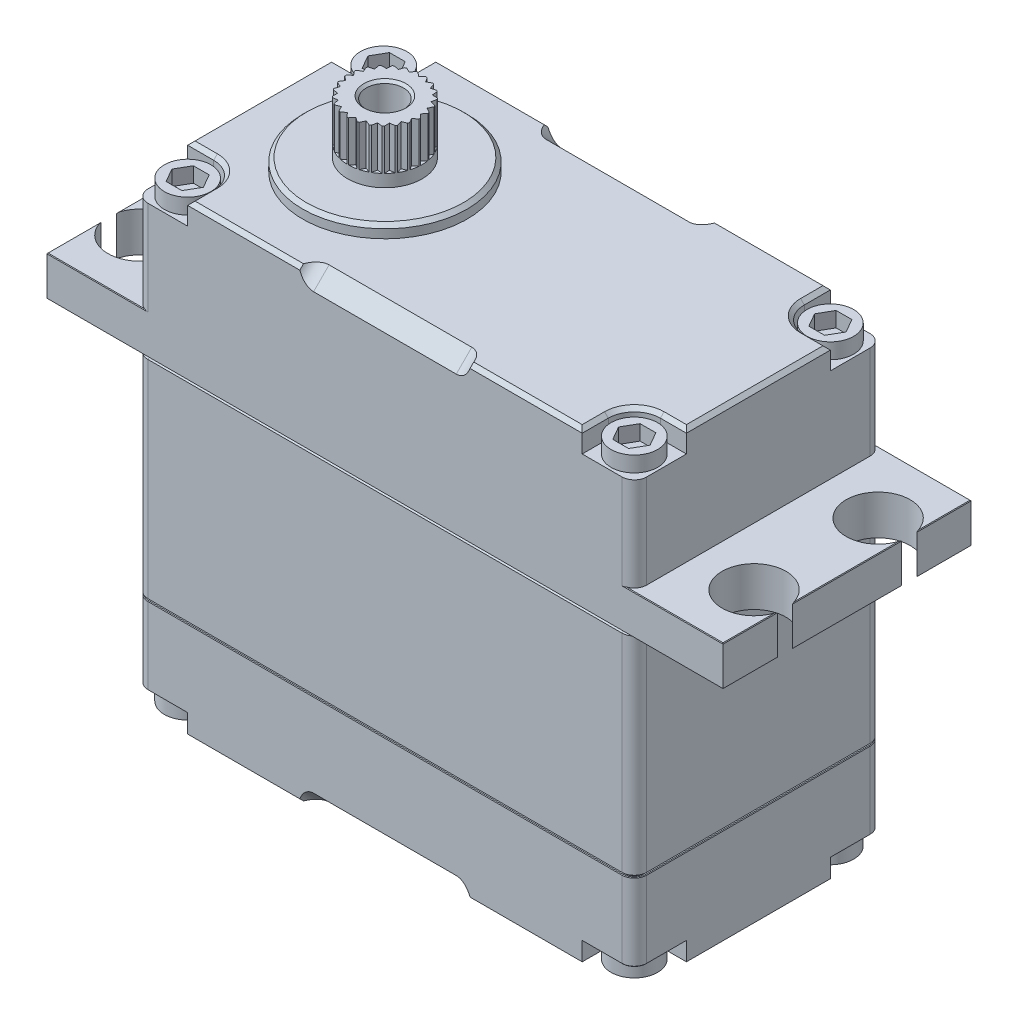
SolidWorks part; units mm, degrees
material "Nylon 101"
ref_plane "Front Plane" through (0, 0, 0) normal (0, 0, 1) x (1, 0, 0)
ref_plane "Top Plane" through (0, 0, 0) normal (0, 1, 0) x (1, 0, 0)
ref_plane "Right Plane" through (0, 0, 0) normal (1, 0, 0) x (0, 0, -1)
sketch "Sketch1" plane through (0, 0, 0) normal (0, 1, 0) x (1, 0, 0)
  line L1 (0, 0) -> (40.2, 0)
  line L2 (0, 0) -> (0, 20)
  line L3 (0, 20) -> (40.2, 20)
  line L4 (40.2, 0) -> (40.2, 20)
  dimension "D1" = 20
  dimension "D2" = 40.2
extrude "Boss-Extrude1" add sketch "Sketch1" along normal blind 9.3
sketch "Sketch2" plane through (0, 0, 0) normal (0, -1, 0) x (1, 0, 0)
  line L0 (40.2, -20) -> (0, -20) construction
  line L1 (-7.15, 0) -> (47.35, 0)
  line L2 (-7.15, 0) -> (-7.15, -20)
  line L3 (-7.15, -20) -> (47.35, -20)
  line L4 (47.35, 0) -> (47.35, -20)
  line L6 (0, 0) -> (40.2, 0) construction
  point P8 (20.1, 0)
  point P9 (20.1, 0)
  dimension "D1" = 54.5
extrude "Boss-Extrude2" add sketch "Sketch2" along normal blind 3.2
sketch "Sketch3" plane through (0, -3.2, 0) normal (0, -1, 0) x (1, 0, 0)
  line L4 (0, 0) -> (0, -20)
  line L5 (40.2, 0) -> (0, 0)
  line L6 (40.2, -20) -> (40.2, 0)
  line L7 (0, -20) -> (40.2, -20)
  line L8 (0, 0) -> (0, -20)
  line L9 (40.2, 0) -> (0, 0)
  line L10 (40.2, -20) -> (40.2, 0)
  line L11 (0, -20) -> (40.2, -20)
  dimension "D1" = 0
extrude "Boss-Extrude3" add sketch "Sketch3" along normal blind 17 separate body
sketch "Sketch4" plane through (0, -20.2, 0) normal (0, -1, 0) x (1, 0, 0)
  line L4 (0, -20) -> (40.2, -20)
  line L5 (40.2, -20) -> (40.2, 0)
  line L6 (40.2, 0) -> (0, 0)
  line L7 (0, 0) -> (0, -20)
  line L8 (0, -20) -> (40.2, -20)
  line L9 (40.2, -20) -> (40.2, 0)
  line L10 (40.2, 0) -> (0, 0)
  line L11 (0, 0) -> (0, -20)
  dimension "D1" = 0
extrude "Boss-Extrude5" add sketch "Sketch4" along normal blind 8 separate body
sketch "Sketch5" plane through (0, 9.3, 0) normal (0, 1, 0) x (1, 0, 0)
  line L0 (-7.15, 0) -> (-7.15, 20) construction
  circle A0 centre (10.1, 10) radius 6.625
  point P4 (-7.15, 10)
  dimension "D1" = 13.25
  dimension "D2" = 17.25
extrude "Boss-Extrude6" add sketch "Sketch5" along normal blind 1
sketch "Sketch6" plane through (0, 10.3, 0) normal (0, 1, 0) x (1, 0, 0)
  circle A0 centre (10.1, 10) radius 3
  circle A1 centre (10.1, 10) radius 6.625
  circle A2 centre (10.1, 10) radius 6.625 construction
  dimension "D2" = 6
  dimension "D1" = 0
extrude "Boss-Extrude7" add sketch "Sketch6" along normal blind 4.3 separate body
sketch "Sketch7" plane through (0, 0, 0) normal (0, 1, 0) x (1, 0, 0)
  line L0 (40.2, 20) -> (0, 20) construction
  line L1 (-4.65, 15) -> (44.85, 15) construction
  line L2 (-4.65, 15) -> (-4.65, 5) construction
  line L3 (-4.65, 5) -> (44.85, 5) construction
  line L4 (44.85, 15) -> (44.85, 5) construction
  line L5 (20.1, 20) -> (20.1, 0) construction
  line L6 (0, 0) -> (40.2, 0) construction
  circle A0 centre (-4.65, 5) radius 2.575
  circle A1 centre (-4.65, 15) radius 2.575
  circle A2 centre (44.85, 15) radius 2.575
  circle A3 centre (44.85, 5) radius 2.575
  point P10 (20.1, 20)
  point P11 (20.1, 15)
  point P16 (20.1, 10)
  point P17 (44.85, 10)
  dimension "D3" = 5.15
  dimension "D1" = 49.5
  dimension "D2" = 10
extrude "Cut-Extrude1" cut sketch "Sketch7" against normal up to next (3.2 mm away)
sketch "Sketch9" plane through (0, 14.6, 0) normal (0, 1, 0) x (1, 0, 0)
  circle A0 centre (10.1, 10) radius 1.5
  dimension "D1" = 3
extrude "Cut-Extrude3" cut sketch "Sketch9" against normal blind 4
chamfer "Chamfer1" distance 0.2 angle 45 1 edges at (10.1, 14.6, -8.5)
sketch "Sketch10" plane through (40.2, 0, 0) normal (1, 0, 0) x (0, 0, -1)
  line L1 (7, -20.2) -> (13, -20.2)
  line L2 (7, -20.2) -> (7, -23.2)
  line L3 (7, -23.2) -> (13, -23.2)
  line L4 (13, -20.2) -> (13, -23.2)
  line L5 (20, -20.2) -> (0, -20.2) construction
  point P9 (10, -20.2)
  point P10 (10, -20.2)
  dimension "D1" = 3
  dimension "D2" = 6
extrude "Boss-Extrude8" add sketch "Sketch10" against normal blind 5 from surface at -40.2 separate body starting at face at (0, -24.2, -10)
sketch "Sketch8" plane through (0, 14.6, 0) normal (0, 1, 0) x (1, 0, 0)
  line L0 (10.1, 10) -> (10.1, 13) construction
  line L1 (9.775, 13) -> (10.425, 13)
  line L2 (10.425, 13) -> (10.1, 12.7)
  line L3 (10.1, 12.7) -> (9.775, 13)
  line L4 (10.7715, 12.6152) -> (10.5313, 12.9866)
  line L5 (10.5313, 12.9866) -> (11.1609, 12.8249)
  line L6 (11.1609, 12.8249) -> (10.7715, 12.6152)
  line L7 (11.4007, 12.366) -> (11.2605, 12.7855)
  line L8 (11.2605, 12.7855) -> (11.8301, 12.4724)
  line L9 (11.8301, 12.4724) -> (11.4007, 12.366)
  line L10 (11.9483, 11.9682) -> (11.9167, 12.4094)
  line L11 (11.9167, 12.4094) -> (12.3906, 11.9644)
  line L12 (12.3906, 11.9644) -> (11.9483, 11.9682)
  line L13 (12.3797, 11.4467) -> (12.4588, 11.8819)
  line L14 (12.4588, 11.8819) -> (12.8071, 11.3331)
  line L15 (12.8071, 11.3331) -> (12.3797, 11.4467)
  line L16 (12.6679, 10.8343) -> (12.8527, 11.2361)
  line L17 (12.8527, 11.2361) -> (13.0536, 10.618)
  line L18 (13.0536, 10.618) -> (12.6679, 10.8343)
  line L19 (12.7947, 10.1695) -> (13.0737, 10.5127)
  line L20 (13.0737, 10.5127) -> (13.1145, 9.864)
  line L21 (13.1145, 9.864) -> (12.7947, 10.1695)
  line L22 (12.7522, 9.4941) -> (13.1078, 9.7571)
  line L23 (13.1078, 9.7571) -> (12.986, 9.1186)
  line L24 (12.986, 9.1186) -> (12.7522, 9.4941)
  line L25 (12.543, 8.8504) -> (12.9529, 9.0167)
  line L26 (12.9529, 9.0167) -> (12.6761, 8.4286)
  line L27 (12.6761, 8.4286) -> (12.543, 8.8504)
  line L28 (12.1804, 8.279) -> (12.6187, 8.3381)
  line L29 (12.6187, 8.3381) -> (12.2044, 7.8373)
  line L30 (12.2044, 7.8373) -> (12.1804, 8.279)
  line L31 (11.687, 7.8157) -> (12.1263, 7.764)
  line L32 (12.1263, 7.764) -> (11.6004, 7.3819)
  line L33 (11.6004, 7.3819) -> (11.687, 7.8157)
  line L34 (11.0939, 7.4896) -> (11.5066, 7.3303)
  line L35 (11.5066, 7.3303) -> (10.9022, 7.091)
  line L36 (10.9022, 7.091) -> (11.0939, 7.4896)
  line L37 (10.4384, 7.3213) -> (10.7984, 7.0644)
  line L38 (10.7984, 7.0644) -> (10.1536, 6.9829)
  line L39 (10.1536, 6.9829) -> (10.4384, 7.3213)
  line L40 (9.7616, 7.3213) -> (10.0464, 6.9829)
  line L41 (10.0464, 6.9829) -> (9.4016, 7.0644)
  line L42 (9.4016, 7.0644) -> (9.7616, 7.3213)
  line L43 (9.1061, 7.4896) -> (9.2978, 7.091)
  line L44 (9.2978, 7.091) -> (8.6934, 7.3303)
  line L45 (8.6934, 7.3303) -> (9.1061, 7.4896)
  line L46 (8.513, 7.8157) -> (8.5996, 7.3819)
  line L47 (8.5996, 7.3819) -> (8.0737, 7.764)
  line L48 (8.0737, 7.764) -> (8.513, 7.8157)
  line L49 (8.0196, 8.279) -> (7.9956, 7.8373)
  line L50 (7.9956, 7.8373) -> (7.5813, 8.3381)
  line L51 (7.5813, 8.3381) -> (8.0196, 8.279)
  line L52 (7.657, 8.8504) -> (7.5239, 8.4286)
  line L53 (7.5239, 8.4286) -> (7.2471, 9.0167)
  line L54 (7.2471, 9.0167) -> (7.657, 8.8504)
  line L55 (7.4478, 9.4941) -> (7.214, 9.1186)
  line L56 (7.214, 9.1186) -> (7.0922, 9.7571)
  line L57 (7.0922, 9.7571) -> (7.4478, 9.4941)
  line L58 (7.4053, 10.1695) -> (7.0855, 9.864)
  line L59 (7.0855, 9.864) -> (7.1263, 10.5127)
  line L60 (7.1263, 10.5127) -> (7.4053, 10.1695)
  line L61 (7.5321, 10.8343) -> (7.1464, 10.618)
  line L62 (7.1464, 10.618) -> (7.3473, 11.2361)
  line L63 (7.3473, 11.2361) -> (7.5321, 10.8343)
  line L64 (7.8203, 11.4467) -> (7.3929, 11.3331)
  line L65 (7.3929, 11.3331) -> (7.7412, 11.8819)
  line L66 (7.7412, 11.8819) -> (7.8203, 11.4467)
  line L67 (8.2517, 11.9682) -> (7.8094, 11.9644)
  line L68 (7.8094, 11.9644) -> (8.2833, 12.4094)
  line L69 (8.2833, 12.4094) -> (8.2517, 11.9682)
  line L70 (8.7993, 12.366) -> (8.3699, 12.4724)
  line L71 (8.3699, 12.4724) -> (8.9395, 12.7855)
  line L72 (8.9395, 12.7855) -> (8.7993, 12.366)
  line L73 (9.4285, 12.6152) -> (9.0391, 12.8249)
  line L74 (9.0391, 12.8249) -> (9.6687, 12.9866)
  line L75 (9.6687, 12.9866) -> (9.4285, 12.6152)
  circle A0 centre (10.1, 10) radius 3 construction
  point P7 (10.1, 13)
  point P84 (10.1, 10)
  dimension "D1" = 0.3
  dimension "D2" = 0.65
  dimension "D3" = 25
extrude "Cut-Extrude2" cut sketch "Sketch8" against normal blind 3.3
sketch "Sketch11" plane through (0, 9.3, 0) normal (0, 1, 0) x (1, 0, 0)
  line L0 (20.1, 20) -> (20.1, 0) construction
  line L1 (40.2, 20) -> (0, 20) construction
  line L2 (0, 0) -> (40.2, 0) construction
  line L3 (0, 10) -> (40.2, 10) construction
  line L4 (0, 20) -> (0, 0) construction
  line L5 (40.2, 0) -> (40.2, 20) construction
  line L6 (36, 2.1) -> (36, 0)
  line L7 (36, 0) -> (40.2, 0)
  line L9 (38.1, 4.2) -> (40.2, 4.2)
  line L10 (40.2, 0) -> (40.2, 20) construction
  line L11 (40.2, 4.2) -> (40.2, 0)
  line L12 (38.1, 15.8) -> (40.2, 15.8)
  line L13 (40.2, 15.8) -> (40.2, 20)
  line L14 (36, 20) -> (40.2, 20)
  line L15 (36, 17.9) -> (36, 20)
  line L16 (2.1, 4.2) -> (0, 4.2)
  line L17 (0, 4.2) -> (0, 0)
  line L18 (4.2, 0) -> (0, 0)
  line L19 (4.2, 2.1) -> (4.2, 0)
  line L20 (4.2, 17.9) -> (4.2, 20)
  line L21 (4.2, 20) -> (0, 20)
  line L22 (0, 15.8) -> (0, 20)
  line L23 (2.1, 15.8) -> (0, 15.8)
  arc A0 (38.1, 4.2) -> (36, 2.1) centre (38.1, 2.1) ccw
  arc A1 (38.1, 15.8) -> (36, 17.9) centre (38.1, 17.9) cw
  arc A2 (2.1, 4.2) -> (4.2, 2.1) centre (2.1, 2.1) cw
  arc A3 (2.1, 15.8) -> (4.2, 17.9) centre (2.1, 17.9) ccw
  dimension "D1" = 4.2
extrude "Cut-Extrude4" cut sketch "Sketch11" against normal blind 1.75
sketch "Sketch13" plane through (0, -28.2, 0) normal (0, -1, 0) x (1, 0, 0)
  line L0 (38.1, -15.8) -> (40.2, -15.8) construction
  line L1 (40.2, -15.8) -> (40.2, -20) construction
  line L2 (40.2, -20) -> (36, -20) construction
  line L3 (36, -20) -> (36, -17.9) construction
  line L4 (36, -2.1) -> (36, 0) construction
  line L5 (36, 0) -> (40.2, 0) construction
  line L6 (40.2, 0) -> (40.2, -4.2) construction
  line L7 (40.2, -4.2) -> (38.1, -4.2) construction
  line L8 (2.1, -4.2) -> (0, -4.2) construction
  line L9 (0, -4.2) -> (0, 0) construction
  line L10 (0, 0) -> (4.2, 0) construction
  line L11 (4.2, 0) -> (4.2, -2.1) construction
  line L12 (4.2, -17.9) -> (4.2, -20) construction
  line L13 (4.2, -20) -> (0, -20) construction
  line L14 (0, -20) -> (0, -15.8) construction
  line L15 (0, -15.8) -> (2.1, -15.8) construction
  line L16 (38.1, -15.8) -> (40.2, -15.8)
  line L17 (40.2, -15.8) -> (40.2, -20)
  line L18 (40.2, -20) -> (36, -20)
  line L19 (36, -20) -> (36, -17.9)
  line L20 (36, -2.1) -> (36, 0)
  line L21 (36, 0) -> (40.2, 0)
  line L22 (40.2, 0) -> (40.2, -4.2)
  line L23 (40.2, -4.2) -> (38.1, -4.2)
  line L24 (2.1, -4.2) -> (0, -4.2)
  line L25 (0, -4.2) -> (0, 0)
  line L26 (0, 0) -> (4.2, 0)
  line L27 (4.2, 0) -> (4.2, -2.1)
  line L28 (4.2, -17.9) -> (4.2, -20)
  line L29 (4.2, -20) -> (0, -20)
  line L30 (0, -20) -> (0, -15.8)
  line L31 (0, -15.8) -> (2.1, -15.8)
  arc A0 (38.1, -15.8) -> (36, -17.9) centre (38.1, -17.9) ccw construction
  arc A1 (36, -2.1) -> (38.1, -4.2) centre (38.1, -2.1) ccw construction
  arc A2 (2.1, -4.2) -> (4.2, -2.1) centre (2.1, -2.1) ccw construction
  arc A3 (4.2, -17.9) -> (2.1, -15.8) centre (2.1, -17.9) ccw construction
  arc A4 (38.1, -15.8) -> (36, -17.9) centre (38.1, -17.9) ccw
  arc A5 (36, -2.1) -> (38.1, -4.2) centre (38.1, -2.1) ccw
  arc A6 (2.1, -4.2) -> (4.2, -2.1) centre (2.1, -2.1) ccw
  arc A7 (4.2, -17.9) -> (2.1, -15.8) centre (2.1, -17.9) ccw
extrude "Cut-Extrude6" cut sketch "Sketch13" against normal blind 1.75
sketch "Sketch12" plane through (0, 9.3, 0) normal (0, 1, 0) x (1, 0, 0)
  line L0 (0, 10) -> (40.2, 10) construction
  line L1 (0, 15.8) -> (0, 4.2) construction
  line L2 (40.2, 4.2) -> (40.2, 15.8) construction
  line L3 (36, 20) -> (4.2, 20) construction
  line L4 (13.1, 20) -> (27.1, 20)
  line L5 (13.1, 20) -> (13.1, 18.75)
  line L6 (13.1, 18.75) -> (27.1, 18.75)
  line L7 (27.1, 20) -> (27.1, 18.75)
  line L8 (13.1, 1.25) -> (27.1, 1.25)
  line L9 (27.1, 0) -> (27.1, 1.25)
  line L10 (13.1, 0) -> (27.1, 0)
  line L11 (13.1, 0) -> (13.1, 1.25)
  point P12 (20.1, 20)
  point P13 (20.1, 10)
  dimension "D1" = 1.25
  dimension "D2" = 14
extrude "Cut-Extrude5" cut sketch "Sketch12" against normal blind 1.25
sketch "Sketch14" plane through (0, -28.2, 0) normal (0, -1, 0) x (1, 0, 0)
  line L0 (13.1, -20) -> (13.1, -18.75) construction
  line L1 (13.1, -18.75) -> (27.1, -18.75) construction
  line L2 (27.1, -18.75) -> (27.1, -20) construction
  line L3 (27.1, -20) -> (13.1, -20) construction
  line L4 (13.1, -1.25) -> (13.1, 0) construction
  line L5 (13.1, 0) -> (27.1, 0) construction
  line L6 (27.1, 0) -> (27.1, -1.25) construction
  line L7 (27.1, -1.25) -> (13.1, -1.25) construction
  line L8 (13.1, -20) -> (13.1, -18.75)
  line L9 (13.1, -18.75) -> (27.1, -18.75)
  line L10 (27.1, -18.75) -> (27.1, -20)
  line L11 (27.1, -20) -> (13.1, -20)
  line L12 (13.1, -1.25) -> (13.1, 0)
  line L13 (13.1, 0) -> (27.1, 0)
  line L14 (27.1, 0) -> (27.1, -1.25)
  line L15 (27.1, -1.25) -> (13.1, -1.25)
extrude "Cut-Extrude7" cut sketch "Sketch14" against normal blind 1.25
chamfer "Chamfer2" distance 1.25 angle 45 2 edges at (20.1, 8.05, -1.25) (20.1, 8.05, -18.75)
chamfer "Chamfer3" distance 1.25 angle 45 2 edges at (20.1, -26.95, -1.25) (20.1, -26.95, -18.75)
fillet "Fillet1" radius 1.25 4 edges at (13.1, 8.675, -0.625) (27.1, 8.675, -0.625) (13.1, 8.675, -19.375) (27.1, 8.675, -19.375)
chamfer "Chamfer5" distance 0.3 angle 45 19 edges at (31.5226, 9.3, 0) (39.15, 9.3, -4.2) (36, 9.3, -1.05) (36.6151, 9.3, -3.5849) (40.2, 9.3, -10) (36, 9.3, -18.95) (39.15, 9.3, -15.8) (36.6151, 9.3, -16.4151) (31.5226, 9.3, -20) (1.05, 9.3, -15.8) (4.2, 9.3, -18.95) (3.5849, 9.3, -16.4151) (8.6774, 9.3, -20) (0, 9.3, -10) (4.2, 9.3, -1.05) (1.05, 9.3, -4.2) (3.5849, 9.3, -3.5849) (8.6774, 9.3, 0) (10.1, 10.3, -3.375)
fillet "Fillet2" radius 1.25 4 edges at (13.1, -27.575, -19.375) (27.1, -27.575, -19.375) (27.1, -27.575, -0.625) (13.1, -27.575, -0.625)
chamfer "Chamfer6" distance 0.3 angle 45 18 edges at (40.2, -28.2, -10) (36, -28.2, -1.05) (39.15, -28.2, -4.2) (36.6151, -28.2, -3.5849) (31.5226, -28.2, 0) (39.15, -28.2, -15.8) (36.6151, -28.2, -16.4151) (36, -28.2, -18.95) (31.5226, -28.2, -20) (8.6774, -28.2, -20) (4.2, -28.2, -18.95) (3.5849, -28.2, -16.4151) (1.05, -28.2, -15.8) (0, -28.2, -10) (1.05, -28.2, -4.2) (3.5849, -28.2, -3.5849) (4.2, -28.2, -1.05) (8.6774, -28.2, 0)
fillet "Fillet3" radius 1 4 edges at (40.2, -11.7, 0) (40.2, -11.7, -20) (0, -11.7, 0) (0, -11.7, -20)
fillet "Fillet4" radius 1 4 edges at (0, -23.325, 0) (40.2, -23.325, 0) (40.2, -23.325, -20) (0, -23.325, -20)
fillet "Fillet5" radius 1 4 edges at (0, 3.775, 0) (0, 3.775, -20) (40.2, 3.775, -20) (40.2, 3.775, 0)
sketch "Sketch15" plane through (0, 7.55, 0) normal (0, 1, 0) x (1, 0, 0)
  line L0 (40.2, 15.8) -> (40.2, 19) construction
  line L1 (39.2, 20) -> (36, 20) construction
  line L2 (36, 20) -> (36, 17.9) construction
  line L3 (38.1, 15.8) -> (40.2, 15.8) construction
  line L4 (4.2, 20) -> (1, 20) construction
  line L5 (0, 19) -> (0, 15.8) construction
  line L6 (0, 15.8) -> (2.1, 15.8) construction
  line L7 (4.2, 17.9) -> (4.2, 20) construction
  line L8 (0, 4.2) -> (0, 1) construction
  line L9 (1, 0) -> (4.2, 0) construction
  line L10 (4.2, 0) -> (4.2, 2.1) construction
  line L11 (2.1, 4.2) -> (0, 4.2) construction
  line L12 (36, 0) -> (39.2, 0) construction
  line L13 (40.2, 1) -> (40.2, 4.2) construction
  line L14 (40.2, 4.2) -> (38.1, 4.2) construction
  line L15 (36, 2.1) -> (36, 0) construction
  line L16 (40.2, 15.8) -> (40.2, 19) construction
  line L17 (39.2, 20) -> (36, 20) construction
  line L18 (36, 20) -> (36, 17.9) construction
  line L19 (38.1, 15.8) -> (40.2, 15.8) construction
  line L20 (4.2, 20) -> (1, 20) construction
  line L21 (0, 19) -> (0, 15.8) construction
  line L22 (0, 15.8) -> (2.1, 15.8) construction
  line L23 (4.2, 17.9) -> (4.2, 20) construction
  line L24 (0, 4.2) -> (0, 1) construction
  line L25 (1, 0) -> (4.2, 0) construction
  line L26 (4.2, 0) -> (4.2, 2.1) construction
  line L27 (2.1, 4.2) -> (0, 4.2) construction
  line L28 (36, 0) -> (39.2, 0) construction
  line L29 (40.2, 1) -> (40.2, 4.2) construction
  line L30 (40.2, 4.2) -> (38.1, 4.2) construction
  line L31 (36, 2.1) -> (36, 0) construction
  arc A0 (40.2, 19) -> (39.2, 20) centre (39.2, 19) ccw construction
  arc A1 (36, 17.9) -> (38.1, 15.8) centre (38.1, 17.9) ccw construction
  arc A2 (1, 20) -> (0, 19) centre (1, 19) ccw construction
  arc A3 (2.1, 15.8) -> (4.2, 17.9) centre (2.1, 17.9) ccw construction
  arc A4 (0, 1) -> (1, 0) centre (1, 1) ccw construction
  arc A5 (4.2, 2.1) -> (2.1, 4.2) centre (2.1, 2.1) ccw construction
  arc A6 (39.2, 0) -> (40.2, 1) centre (39.2, 1) ccw construction
  arc A7 (38.1, 4.2) -> (36, 2.1) centre (38.1, 2.1) ccw construction
  arc A8 (40.2, 19) -> (39.2, 20) centre (39.2, 19) ccw construction
  arc A9 (36, 17.9) -> (38.1, 15.8) centre (38.1, 17.9) ccw construction
  arc A10 (1, 20) -> (0, 19) centre (1, 19) ccw construction
  arc A11 (2.1, 15.8) -> (4.2, 17.9) centre (2.1, 17.9) ccw construction
  arc A12 (0, 1) -> (1, 0) centre (1, 1) ccw construction
  arc A13 (4.2, 2.1) -> (2.1, 4.2) centre (2.1, 2.1) ccw construction
  arc A14 (39.2, 0) -> (40.2, 1) centre (39.2, 1) ccw construction
  arc A15 (38.1, 4.2) -> (36, 2.1) centre (38.1, 2.1) ccw construction
  circle A16 centre (2.1, 2.1) radius 1.875
  circle A17 centre (2.1, 17.9) radius 1.875
  circle A18 centre (38.1, 17.9) radius 1.875
  circle A19 centre (38.1, 2.1) radius 1.875
  dimension "D1" = 3.75
extrude "Boss-Extrude10" add sketch "Sketch15" along normal blind 1.25 separate body
sketch "Sketch16" plane through (0, -26.45, 0) normal (0, -1, 0) x (1, 0, 0)
  circle A0 centre (2.1, -2.1) radius 1.875 construction
  circle A1 centre (38.1, -2.1) radius 1.875 construction
  circle A2 centre (38.1, -17.9) radius 1.875 construction
  circle A3 centre (2.1, -17.9) radius 1.875 construction
  circle A4 centre (2.1, -2.1) radius 1.875
  circle A5 centre (38.1, -2.1) radius 1.875
  circle A6 centre (38.1, -17.9) radius 1.875
  circle A7 centre (2.1, -17.9) radius 1.875
extrude "Boss-Extrude12" add sketch "Sketch16" along normal blind 1.25 separate body
chamfer "Chamfer8" distance 0.15 angle 45 16 edges at (39.9071, -20.2, -19.7071) (40.2, -20.2, -10) (20.1, -20.2, -20) (39.9071, -20.2, -0.2929) (0.2929, -20.2, -19.7071) (20.1, -20.2, 0) (0, -20.2, -10) (0.2929, -20.2, -0.2929) (40.2, -3.2, -10) (39.9071, -3.2, -0.2929) (39.9071, -3.2, -19.7071) (20.1, -3.2, 0) (20.1, -3.2, -20) (0.2929, -3.2, -0.2929) (0.2929, -3.2, -19.7071) (0, -3.2, -10)
sketch "Sketch18" plane through (0, 8.8, 0) normal (0, 1, 0) x (1, 0, 0)
  line L0 (0.3, 10) -> (39.9, 10) construction
  line L1 (0.3, 15.5) -> (0.3, 4.5) construction
  line L2 (39.9, 4.5) -> (39.9, 15.5) construction
  line L3 (20.1, 18.75) -> (20.1, 1.25) construction
  line L4 (14.35, 18.75) -> (25.85, 18.75) construction
  line L5 (25.85, 1.25) -> (14.35, 1.25) construction
  line L6 (2.7351, 3.2) -> (3.3702, 2.1)
  line L7 (3.3702, 17.9) -> (2.7351, 19)
  line L8 (2.7351, 19) -> (1.4649, 19)
  line L9 (1.4649, 19) -> (0.8298, 17.9)
  line L10 (0.8298, 17.9) -> (1.4649, 16.8)
  line L11 (1.4649, 16.8) -> (2.7351, 16.8)
  line L12 (2.7351, 16.8) -> (3.3702, 17.9)
  line L13 (1.4649, 3.2) -> (2.7351, 3.2)
  line L14 (0.8298, 2.1) -> (1.4649, 3.2)
  line L15 (1.4649, 1) -> (0.8298, 2.1)
  line L16 (2.7351, 1) -> (1.4649, 1)
  line L17 (3.3702, 2.1) -> (2.7351, 1)
  line L18 (38.7351, 3.2) -> (37.4649, 3.2)
  line L19 (39.3702, 2.1) -> (38.7351, 3.2)
  line L20 (38.7351, 1) -> (39.3702, 2.1)
  line L21 (37.4649, 1) -> (38.7351, 1)
  line L22 (36.8298, 2.1) -> (37.4649, 1)
  line L23 (37.4649, 3.2) -> (36.8298, 2.1)
  line L24 (37.4649, 16.8) -> (36.8298, 17.9)
  line L25 (38.7351, 16.8) -> (37.4649, 16.8)
  line L26 (39.3702, 17.9) -> (38.7351, 16.8)
  line L27 (38.7351, 19) -> (39.3702, 17.9)
  line L28 (37.4649, 19) -> (38.7351, 19)
  line L29 (36.8298, 17.9) -> (37.4649, 19)
  circle A1 centre (2.1, 17.9) radius 1.1 construction
  circle A2 centre (2.1, 17.9) radius 1.875
  circle A3 centre (2.1, 17.9) radius 1.875 construction
  dimension "D1" = 0
  dimension "D2" = 2.2
extrude "Cut-Extrude8" cut sketch "Sketch18" against normal blind 1.22
sketch "Sketch19" plane through (0, -27.7, 0) normal (0, -1, 0) x (1, 0, 0)
  line L0 (37.4649, -16.8) -> (38.7351, -16.8) construction
  line L1 (38.7351, -16.8) -> (39.3702, -17.9) construction
  line L2 (39.3702, -17.9) -> (38.7351, -19) construction
  line L3 (38.7351, -19) -> (37.4649, -19) construction
  line L4 (37.4649, -19) -> (36.8298, -17.9) construction
  line L5 (36.8298, -17.9) -> (37.4649, -16.8) construction
  line L6 (39.3702, -2.1) -> (38.7351, -3.2) construction
  line L7 (38.7351, -3.2) -> (37.4649, -3.2) construction
  line L8 (37.4649, -3.2) -> (36.8298, -2.1) construction
  line L9 (36.8298, -2.1) -> (37.4649, -1) construction
  line L10 (37.4649, -1) -> (38.7351, -1) construction
  line L11 (38.7351, -1) -> (39.3702, -2.1) construction
  line L12 (2.7351, -3.2) -> (1.4649, -3.2) construction
  line L13 (1.4649, -3.2) -> (0.8298, -2.1) construction
  line L14 (0.8298, -2.1) -> (1.4649, -1) construction
  line L15 (1.4649, -1) -> (2.7351, -1) construction
  line L16 (2.7351, -1) -> (3.3702, -2.1) construction
  line L17 (3.3702, -2.1) -> (2.7351, -3.2) construction
  line L18 (2.7351, -16.8) -> (3.3702, -17.9) construction
  line L19 (3.3702, -17.9) -> (2.7351, -19) construction
  line L20 (2.7351, -19) -> (1.4649, -19) construction
  line L21 (1.4649, -19) -> (0.8298, -17.9) construction
  line L22 (0.8298, -17.9) -> (1.4649, -16.8) construction
  line L23 (1.4649, -16.8) -> (2.7351, -16.8) construction
  line L24 (37.4649, -16.8) -> (38.7351, -16.8)
  line L25 (38.7351, -16.8) -> (39.3702, -17.9)
  line L26 (39.3702, -17.9) -> (38.7351, -19)
  line L27 (38.7351, -19) -> (37.4649, -19)
  line L28 (37.4649, -19) -> (36.8298, -17.9)
  line L29 (36.8298, -17.9) -> (37.4649, -16.8)
  line L30 (39.3702, -2.1) -> (38.7351, -3.2)
  line L31 (38.7351, -3.2) -> (37.4649, -3.2)
  line L32 (37.4649, -3.2) -> (36.8298, -2.1)
  line L33 (36.8298, -2.1) -> (37.4649, -1)
  line L34 (37.4649, -1) -> (38.7351, -1)
  line L35 (38.7351, -1) -> (39.3702, -2.1)
  line L36 (2.7351, -3.2) -> (1.4649, -3.2)
  line L37 (1.4649, -3.2) -> (0.8298, -2.1)
  line L38 (0.8298, -2.1) -> (1.4649, -1)
  line L39 (1.4649, -1) -> (2.7351, -1)
  line L40 (2.7351, -1) -> (3.3702, -2.1)
  line L41 (3.3702, -2.1) -> (2.7351, -3.2)
  line L42 (2.7351, -16.8) -> (3.3702, -17.9)
  line L43 (3.3702, -17.9) -> (2.7351, -19)
  line L44 (2.7351, -19) -> (1.4649, -19)
  line L45 (1.4649, -19) -> (0.8298, -17.9)
  line L46 (0.8298, -17.9) -> (1.4649, -16.8)
  line L47 (1.4649, -16.8) -> (2.7351, -16.8)
extrude "Cut-Extrude9" cut sketch "Sketch19" against normal blind 1.22
sketch "Sketch23" plane through (0, 14.6, 0) normal (0, 1, 0) x (1, 0, 0)
  line L50 (11.1403, 12.8139) -> (10.7715, 12.6152)
  line L51 (10.7715, 12.6152) -> (10.544, 12.967)
  line L52 (10.4078, 12.9842) -> (10.1, 12.7)
  line L53 (10.1, 12.7) -> (9.7922, 12.9842)
  line L54 (9.656, 12.967) -> (9.4285, 12.6152)
  line L55 (9.4285, 12.6152) -> (9.0597, 12.8139)
  line L56 (8.9321, 12.7633) -> (8.7993, 12.366)
  line L57 (8.7993, 12.366) -> (8.3926, 12.4667)
  line L58 (8.2816, 12.3861) -> (8.2517, 11.9682)
  line L59 (8.2517, 11.9682) -> (7.8328, 11.9646)
  line L60 (7.7453, 11.8589) -> (7.8203, 11.4467)
  line L61 (7.8203, 11.4467) -> (7.4154, 11.3391)
  line L62 (7.357, 11.2149) -> (7.5321, 10.8343)
  line L63 (7.5321, 10.8343) -> (7.1668, 10.6294)
  line L64 (7.1411, 10.4946) -> (7.4053, 10.1695)
  line L65 (7.4053, 10.1695) -> (7.1024, 9.8801)
  line L66 (7.111, 9.7432) -> (7.4478, 9.4941)
  line L67 (7.4478, 9.4941) -> (7.2264, 9.1384)
  line L68 (7.2688, 9.008) -> (7.657, 8.8504)
  line L69 (7.657, 8.8504) -> (7.5309, 8.4509)
  line L70 (7.6044, 8.335) -> (8.0196, 8.279)
  line L71 (8.0196, 8.279) -> (7.9969, 7.8606)
  line L72 (8.0969, 7.7667) -> (8.513, 7.8157)
  line L73 (8.513, 7.8157) -> (8.595, 7.4048)
  line L74 (8.7152, 7.3387) -> (9.1061, 7.4896)
  line L75 (9.1061, 7.4896) -> (9.2877, 7.1121)
  line L76 (9.4206, 7.078) -> (9.7616, 7.3213)
  line L77 (9.7616, 7.3213) -> (10.0314, 7.0008)
  line L78 (10.1686, 7.0008) -> (10.4384, 7.3213)
  line L79 (10.4384, 7.3213) -> (10.7794, 7.078)
  line L80 (10.9123, 7.1121) -> (11.0939, 7.4896)
  line L81 (11.0939, 7.4896) -> (11.4848, 7.3387)
  line L82 (11.605, 7.4048) -> (11.687, 7.8157)
  line L83 (11.687, 7.8157) -> (12.1031, 7.7667)
  line L84 (12.2031, 7.8606) -> (12.1804, 8.279)
  line L85 (12.1804, 8.279) -> (12.5956, 8.335)
  line L86 (12.6691, 8.4509) -> (12.543, 8.8504)
  line L87 (12.543, 8.8504) -> (12.9312, 9.008)
  line L88 (12.9736, 9.1384) -> (12.7522, 9.4941)
  line L89 (12.7522, 9.4941) -> (13.089, 9.7432)
  line L90 (13.0976, 9.8801) -> (12.7947, 10.1695)
  line L91 (12.7947, 10.1695) -> (13.0589, 10.4946)
  line L92 (13.0332, 10.6294) -> (12.6679, 10.8343)
  line L93 (12.6679, 10.8343) -> (12.843, 11.2149)
  line L94 (12.7846, 11.3391) -> (12.3797, 11.4467)
  line L95 (12.3797, 11.4467) -> (12.4547, 11.8589)
  line L96 (12.3672, 11.9646) -> (11.9483, 11.9682)
  line L97 (11.9483, 11.9682) -> (11.9184, 12.3861)
  line L98 (11.8074, 12.4667) -> (11.4007, 12.366)
  line L99 (11.4007, 12.366) -> (11.2679, 12.7633)
  line L100 (11.1403, 12.8139) -> (10.7715, 12.6152)
  line L101 (10.7715, 12.6152) -> (10.544, 12.967)
  line L102 (10.4078, 12.9842) -> (10.1, 12.7)
  line L103 (10.1, 12.7) -> (9.7922, 12.9842)
  line L104 (9.656, 12.967) -> (9.4285, 12.6152)
  line L105 (9.4285, 12.6152) -> (9.0597, 12.8139)
  line L106 (8.9321, 12.7633) -> (8.7993, 12.366)
  line L107 (8.7993, 12.366) -> (8.3926, 12.4667)
  line L108 (8.2816, 12.3861) -> (8.2517, 11.9682)
  line L109 (8.2517, 11.9682) -> (7.8328, 11.9646)
  line L110 (7.7453, 11.8589) -> (7.8203, 11.4467)
  line L111 (7.8203, 11.4467) -> (7.4154, 11.3391)
  line L112 (7.357, 11.2149) -> (7.5321, 10.8343)
  line L113 (7.5321, 10.8343) -> (7.1668, 10.6294)
  line L114 (7.1411, 10.4946) -> (7.4053, 10.1695)
  line L115 (7.4053, 10.1695) -> (7.1024, 9.8801)
  line L116 (7.111, 9.7432) -> (7.4478, 9.4941)
  line L117 (7.4478, 9.4941) -> (7.2264, 9.1384)
  line L118 (7.2688, 9.008) -> (7.657, 8.8504)
  line L119 (7.657, 8.8504) -> (7.5309, 8.4509)
  line L120 (7.6044, 8.335) -> (8.0196, 8.279)
  line L121 (8.0196, 8.279) -> (7.9969, 7.8606)
  line L122 (8.0969, 7.7667) -> (8.513, 7.8157)
  line L123 (8.513, 7.8157) -> (8.595, 7.4048)
  line L124 (8.7152, 7.3387) -> (9.1061, 7.4896)
  line L125 (9.1061, 7.4896) -> (9.2877, 7.1121)
  line L126 (9.4206, 7.078) -> (9.7616, 7.3213)
  line L127 (9.7616, 7.3213) -> (10.0314, 7.0008)
  line L128 (10.1686, 7.0008) -> (10.4384, 7.3213)
  line L129 (10.4384, 7.3213) -> (10.7794, 7.078)
  line L130 (10.9123, 7.1121) -> (11.0939, 7.4896)
  line L131 (11.0939, 7.4896) -> (11.4848, 7.3387)
  line L132 (11.605, 7.4048) -> (11.687, 7.8157)
  line L133 (11.687, 7.8157) -> (12.1031, 7.7667)
  line L134 (12.2031, 7.8606) -> (12.1804, 8.279)
  line L135 (12.1804, 8.279) -> (12.5956, 8.335)
  line L136 (12.6691, 8.4509) -> (12.543, 8.8504)
  line L137 (12.543, 8.8504) -> (12.9312, 9.008)
  line L138 (12.9736, 9.1384) -> (12.7522, 9.4941)
  line L139 (12.7522, 9.4941) -> (13.089, 9.7432)
  line L140 (13.0976, 9.8801) -> (12.7947, 10.1695)
  line L141 (12.7947, 10.1695) -> (13.0589, 10.4946)
  line L142 (13.0332, 10.6294) -> (12.6679, 10.8343)
  line L143 (12.6679, 10.8343) -> (12.843, 11.2149)
  line L144 (12.7846, 11.3391) -> (12.3797, 11.4467)
  line L145 (12.3797, 11.4467) -> (12.4547, 11.8589)
  line L146 (12.3672, 11.9646) -> (11.9483, 11.9682)
  line L147 (11.9483, 11.9682) -> (11.9184, 12.3861)
  line L148 (11.8074, 12.4667) -> (11.4007, 12.366)
  line L149 (11.4007, 12.366) -> (11.2679, 12.7633)
  arc A25 (10.544, 12.967) -> (10.4078, 12.9842) centre (10.1, 10) ccw
  arc A26 (9.7922, 12.9842) -> (9.656, 12.967) centre (10.1, 10) ccw
  arc A27 (9.0597, 12.8139) -> (8.9321, 12.7633) centre (10.1, 10) ccw
  arc A28 (8.3926, 12.4667) -> (8.2816, 12.3861) centre (10.1, 10) ccw
  arc A29 (7.8328, 11.9646) -> (7.7453, 11.8589) centre (10.1, 10) ccw
  arc A30 (7.4154, 11.3391) -> (7.357, 11.2149) centre (10.1, 10) ccw
  arc A31 (7.1668, 10.6294) -> (7.1411, 10.4946) centre (10.1, 10) ccw
  arc A32 (7.1024, 9.8801) -> (7.111, 9.7432) centre (10.1, 10) ccw
  arc A33 (7.2264, 9.1384) -> (7.2688, 9.008) centre (10.1, 10) ccw
  arc A34 (7.5309, 8.4509) -> (7.6044, 8.335) centre (10.1, 10) ccw
  arc A35 (7.9969, 7.8606) -> (8.0969, 7.7667) centre (10.1, 10) ccw
  arc A36 (8.595, 7.4048) -> (8.7152, 7.3387) centre (10.1, 10) ccw
  arc A37 (9.2877, 7.1121) -> (9.4206, 7.078) centre (10.1, 10) ccw
  arc A38 (10.0314, 7.0008) -> (10.1686, 7.0008) centre (10.1, 10) ccw
  arc A39 (10.7794, 7.078) -> (10.9123, 7.1121) centre (10.1, 10) ccw
  arc A40 (11.4848, 7.3387) -> (11.605, 7.4048) centre (10.1, 10) ccw
  arc A41 (12.1031, 7.7667) -> (12.2031, 7.8606) centre (10.1, 10) ccw
  arc A42 (12.5956, 8.335) -> (12.6691, 8.4509) centre (10.1, 10) ccw
  arc A43 (12.9312, 9.008) -> (12.9736, 9.1384) centre (10.1, 10) ccw
  arc A44 (13.089, 9.7432) -> (13.0976, 9.8801) centre (10.1, 10) ccw
  arc A45 (13.0589, 10.4946) -> (13.0332, 10.6294) centre (10.1, 10) ccw
  arc A46 (12.843, 11.2149) -> (12.7846, 11.3391) centre (10.1, 10) ccw
  arc A47 (12.4547, 11.8589) -> (12.3672, 11.9646) centre (10.1, 10) ccw
  arc A48 (11.9184, 12.3861) -> (11.8074, 12.4667) centre (10.1, 10) ccw
  arc A49 (11.2679, 12.7633) -> (11.1403, 12.8139) centre (10.1, 10) ccw
  arc A50 (10.544, 12.967) -> (10.4078, 12.9842) centre (10.1, 10) ccw
  arc A51 (9.7922, 12.9842) -> (9.656, 12.967) centre (10.1, 10) ccw
  arc A52 (9.0597, 12.8139) -> (8.9321, 12.7633) centre (10.1, 10) ccw
  arc A53 (8.3926, 12.4667) -> (8.2816, 12.3861) centre (10.1, 10) ccw
  arc A54 (7.8328, 11.9646) -> (7.7453, 11.8589) centre (10.1, 10) ccw
  arc A55 (7.4154, 11.3391) -> (7.357, 11.2149) centre (10.1, 10) ccw
  arc A56 (7.1668, 10.6294) -> (7.1411, 10.4946) centre (10.1, 10) ccw
  arc A57 (7.1024, 9.8801) -> (7.111, 9.7432) centre (10.1, 10) ccw
  arc A58 (7.2264, 9.1384) -> (7.2688, 9.008) centre (10.1, 10) ccw
  arc A59 (7.5309, 8.4509) -> (7.6044, 8.335) centre (10.1, 10) ccw
  arc A60 (7.9969, 7.8606) -> (8.0969, 7.7667) centre (10.1, 10) ccw
  arc A61 (8.595, 7.4048) -> (8.7152, 7.3387) centre (10.1, 10) ccw
  arc A62 (9.2877, 7.1121) -> (9.4206, 7.078) centre (10.1, 10) ccw
  arc A63 (10.0314, 7.0008) -> (10.1686, 7.0008) centre (10.1, 10) ccw
  arc A64 (10.7794, 7.078) -> (10.9123, 7.1121) centre (10.1, 10) ccw
  arc A65 (11.4848, 7.3387) -> (11.605, 7.4048) centre (10.1, 10) ccw
  arc A66 (12.1031, 7.7667) -> (12.2031, 7.8606) centre (10.1, 10) ccw
  arc A67 (12.5956, 8.335) -> (12.6691, 8.4509) centre (10.1, 10) ccw
  arc A68 (12.9312, 9.008) -> (12.9736, 9.1384) centre (10.1, 10) ccw
  arc A69 (13.089, 9.7432) -> (13.0976, 9.8801) centre (10.1, 10) ccw
  arc A70 (13.0589, 10.4946) -> (13.0332, 10.6294) centre (10.1, 10) ccw
  arc A71 (12.843, 11.2149) -> (12.7846, 11.3391) centre (10.1, 10) ccw
  arc A72 (12.4547, 11.8589) -> (12.3672, 11.9646) centre (10.1, 10) ccw
  arc A73 (11.9184, 12.3861) -> (11.8074, 12.4667) centre (10.1, 10) ccw
  arc A74 (11.2679, 12.7633) -> (11.1403, 12.8139) centre (10.1, 10) ccw
  dimension "D1" = 0
chamfer "Chamfer9" distance 0.05 angle 45 20 edges at (37.6, -26.45, -20) (39.9071, -26.45, -19.7071) (40.2, -26.45, -17.4) (40.2, -26.45, -2.6) (39.9071, -26.45, -0.2929) (37.6, -26.45, 0) (2.6, -26.45, -20) (0.2929, -26.45, -19.7071) (0, -26.45, -17.4) (2.6, -26.45, 0) (0.2929, -26.45, -0.2929) (0, -26.45, -2.6) (20.1, -20.2, -20) (39.9071, -20.2, -19.7071) (0.2929, -20.2, -19.7071) (40.2, -20.2, -10) (0, -20.2, -10) (39.9071, -20.2, -0.2929) (0.2929, -20.2, -0.2929) (20.1, -20.2, 0)
chamfer "Chamfer10" distance 0.05 angle 45 18 edges at (-3.075, 0, 0) (-7.15, 0, -2.1915) (-7.15, 0, -10) (-7.15, 0, -17.8085) (-3.075, 0, -20) (-7.15, -3.2, -10) (43.275, 0, -20) (47.35, 0, -17.8085) (47.35, 0, -10) (43.275, 0, 0) (47.35, 0, -2.1915) (-7.15, -3.2, -2.1915) (20.1, -3.2, 0) (47.35, -3.2, -2.1915) (47.35, -3.2, -10) (-7.15, -3.2, -17.8085) (20.1, -3.2, -20) (47.35, -3.2, -17.8085)
